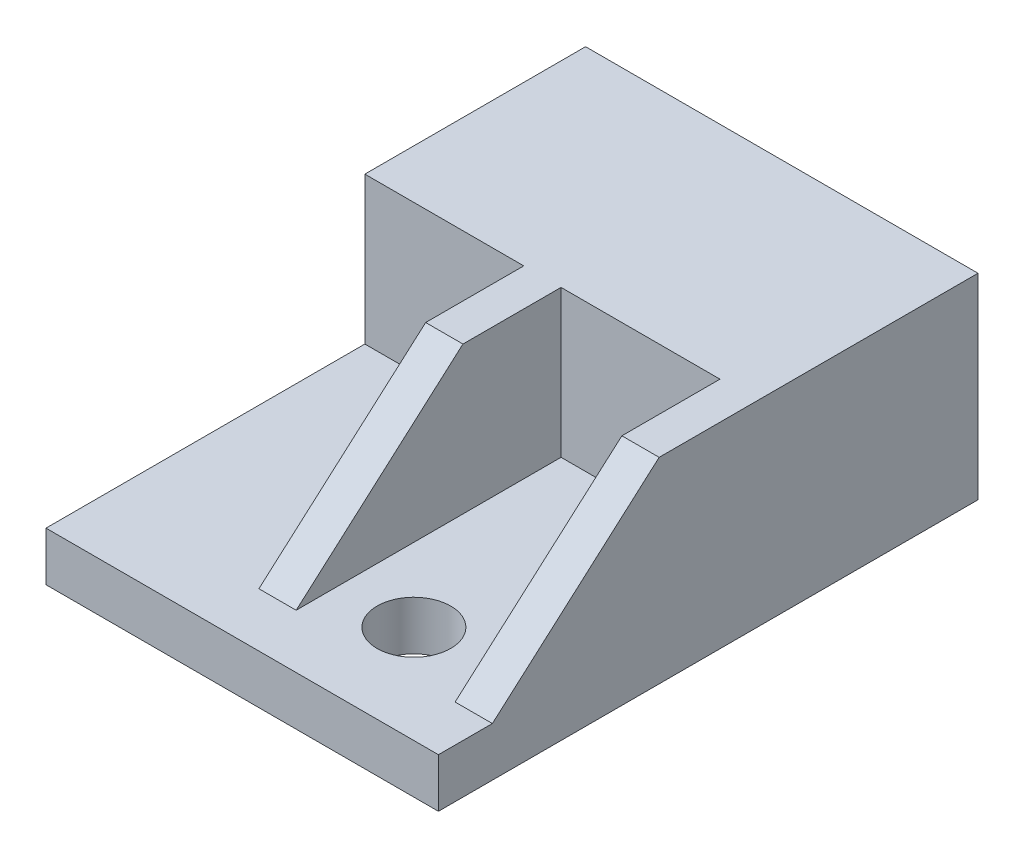
SolidWorks part; units mm, degrees
ref_plane "Front Plane" through (0, 0, 0) normal (0, 0, 1) x (1, 0, 0)
ref_plane "Top Plane" through (0, 0, 0) normal (0, 1, 0) x (1, 0, 0)
ref_plane "Right Plane" through (0, 0, 0) normal (1, 0, 0) x (0, 0, -1)
sketch "Sketch1" plane through (0, 0, 0) normal (0, 1, 0) x (1, 0, 0)
  line L0 (-101.6, 139.7) -> (-101.6, 82.55)
  line L1 (0, 0) -> (-101.6, 0)
  line L2 (0, 0) -> (0, 139.7)
  line L3 (0, 139.7) -> (-101.6, 139.7)
  line L4 (-101.6, 0) -> (-101.6, 139.7)
  line L5 (-60.452, 13.97) -> (-50.8, 13.97)
  line L6 (-9.652, 13.97) -> (0, 13.97)
  line L8 (0, 82.55) -> (0, 139.7)
  line L9 (-9.652, 57.15) -> (0, 57.15)
  line L11 (0, 13.97) -> (0, 82.55)
  line L14 (-50.8, 57.15) -> (-60.452, 57.15)
  line L15 (-60.452, 82.55) -> (-60.452, 13.97)
  line L19 (-50.8, 13.97) -> (-50.8, 82.55)
  line L20 (-50.8, 82.55) -> (-9.652, 82.55)
  line L22 (-9.652, 13.97) -> (-9.652, 82.55)
  line L23 (-60.452, 82.55) -> (-101.6, 82.55)
  circle A0 centre (-31.75, 25.4) radius 9.525
  dimension "D2" = 9.652
  dimension "D7" = 31.75
  dimension "D5" = 19.05
  dimension "D3" = 57.15
  dimension "D4" = 50.8
  dimension "D6" = 13.97
  dimension "D8" = 25.4
  dimension "D9" = 82.55
  dimension "D10" = 139.7
  dimension "D11" = 43.18
  dimension "D12" = 25.4
extrude "Boss-Extrude3" add sketch "Sketch1" along normal blind 50.8 contours L23 L15 L14 L19 L20 L22 L9 L2 L3 L0 region at (-49.1979, 0, -107.911)
extrude "Boss-Extrude5" add sketch "Sketch1<7>" along normal blind 12.7 contours L15 L23 L4 L1 L2 L6 L22 L20 L19 L5 A0 | L5 L19 L14 L15 | L22 L6 L2 L9 region at (-81.026, 0, -81.2409) region at (-55.626, 0, -35.56) region at (-4.826, 0, -35.56)
sketch "Sketch1<7>" plane through (0, 0, 0) normal (0, 1, 0) x (1, 0, 0) same geometry as "Sketch1"
sketch "Sketch3" plane through (0, 0, 0) normal (1, 0, 0) x (0, 0, -1)
  line L1 (57.15, 12.7) -> (13.97, 12.7)
  line L2 (0, 12.7) -> (57.15, 12.7) construction
  line L3 (57.15, 50.8) -> (57.15, 12.7)
  line L4 (57.15, 50.8) -> (13.97, 12.7)
extrude "Boss-Extrude6" add sketch "Sketch3" against normal blind 9.652
sketch "Sketch6" plane through (-50.8, 0, 0) normal (1, 0, 0) x (0, 0, -1)
  line L4 (57.15, 50.8) -> (13.97, 12.7)
  line L6 (57.15, 12.7) -> (13.97, 12.7)
  line L7 (57.15, 12.7) -> (57.15, 50.8)
  line M4 (57.15, 50.8) -> (57.15, 12.7)
sketch "Sketch7" plane through (0, 0, 0) normal (0, -1, 0) x (1, 0, 0)
  line L0 (-95.25, -139.7) -> (-6.35, -139.7)
  line L1 (0, -139.7) -> (-101.6, -139.7) construction
  line L2 (-95.25, -139.7) -> (-95.25, -95.25)
  line L3 (-95.25, -95.25) -> (-6.35, -95.25)
  line L4 (-6.35, -95.25) -> (-6.35, -139.7)
  line L5 (0, 0) -> (0, -139.7) construction
  dimension "D1" = 6.35
  dimension "D2" = 6.35
  dimension "D3" = 44.45
  dimension "D4" = 139.7
extrude "Cut-Extrude1" cut sketch "Sketch7" against normal blind 44.45
extrude "Boss-Extrude7" add sketch "Sketch6" against normal blind 9.652 contours L6 L4 M4 | L7 L4 L6 region at (-50.8, 25.4, -42.7567)
